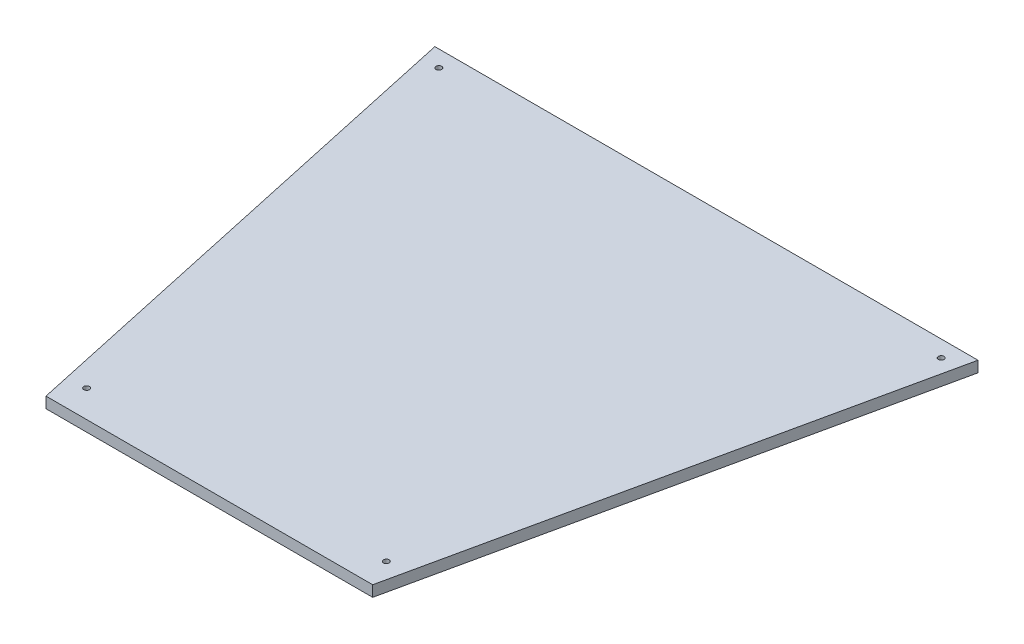
SolidWorks part; units mm, degrees
ref_plane "Front Plane" through (0, 0, 0) normal (0, 0, 1) x (1, 0, 0)
ref_plane "Top Plane" through (0, 0, 0) normal (0, 1, 0) x (1, 0, 0)
ref_plane "Right Plane" through (0, 0, 0) normal (1, 0, 0) x (0, 0, -1)
ref_plane "Plane1" through (0, -28.575, 0) normal (0, -1, 0) x (-1, 0, 0)
sketch "Sketch1" plane through (4.556, 0, 422.8773) normal (0, -1, 0) x (-1, 0, 0)
  line L0 (-184.8912, -195.6635) -> (194.0158, -195.6512)
  line L1 (194.0158, -195.6512) -> (319.5099, 380.9014)
  line L2 (319.5099, 380.9014) -> (-310.4226, 380.881)
  line L3 (-310.4226, 380.881) -> (-184.8912, -195.6635)
  line L4 (-310.4239, 380.881) -> (319.5112, 380.9014) construction
  line L5 (-184.7475, -196.3231) -> (-311.7795, 387.1133) construction
  line L6 (320.8664, 387.1338) -> (193.8722, -196.3108) construction
  line L7 (194.0184, -195.6512) -> (-184.8937, -195.6635) construction
extrude "Boss-Extrude1" add sketch "Sketch1" along normal blind 12.7
sketch "Sketch2" plane through (0, 0, 0) normal (0, 1, 0) x (1, 0, 0)
  circle A28 centre (-173.9972, -586.8788) radius 3.2639
  circle A30 centre (-173.9972, -586.8788) radius 3.2639
  circle A32 centre (173.8926, -587.1937) radius 3.2639
  circle A33 centre (173.8926, -587.1937) radius 3.2639
  circle A34 centre (291.3209, -61.0565) radius 3.2639
  circle A35 centre (291.3209, -61.0565) radius 3.2639
  circle A36 centre (-291.3249, -61.0376) radius 3.2639
  circle A37 centre (-291.3249, -61.0376) radius 3.2639
  dimension "D7" = 0
  dimension "D8" = 0
  dimension "D9" = 0
  dimension "D13" = 0
extrude "Cut-Extrude1" cut sketch "Sketch2" against normal through all
